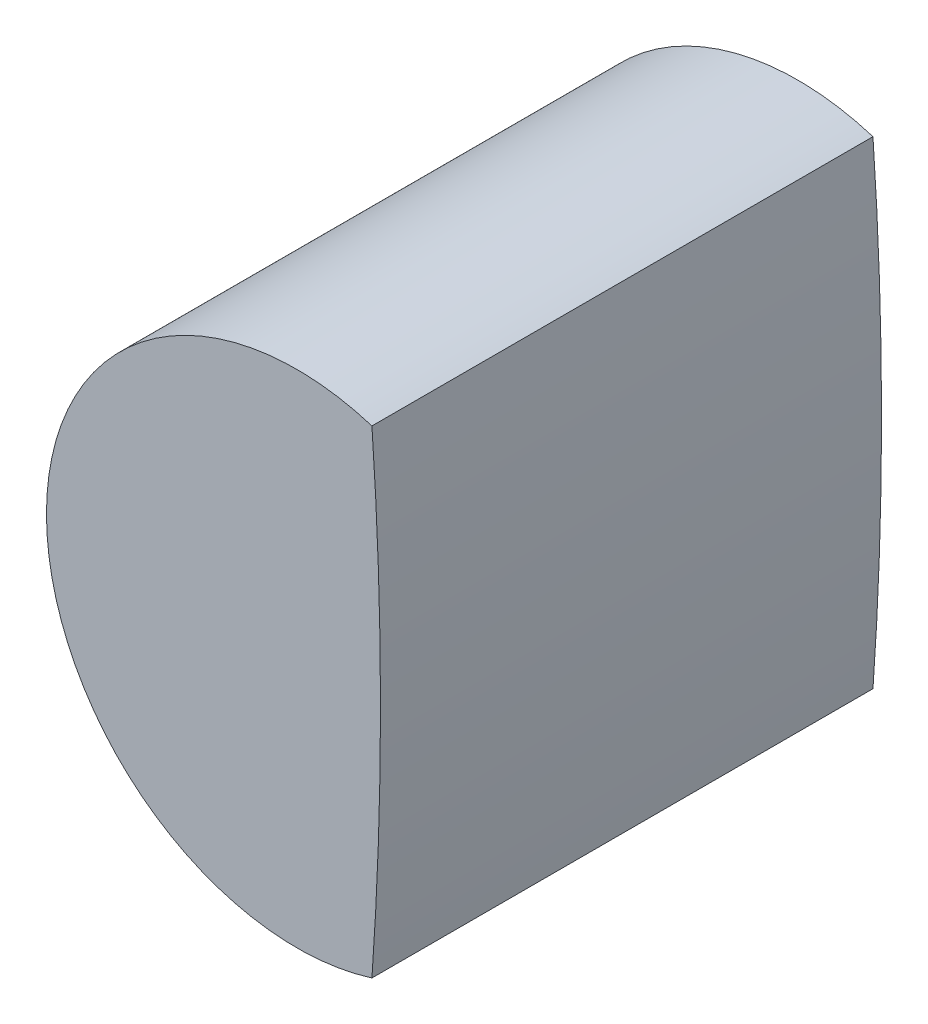
SolidWorks part; units mm, degrees
material "Acrylique (impact moyen-haut)"
ref_plane "Plan de face" through (0, 0, 0) normal (0, 0, 1) x (1, 0, 0)
ref_plane "Plan de dessus" through (0, 0, 0) normal (0, 1, 0) x (1, 0, 0)
ref_plane "Plan de droite" through (0, 0, 0) normal (1, 0, 0) x (0, 0, -1)
sketch "Esquisse1" plane through (0, 0, 0) normal (0, 0, 1) x (1, 0, 0)
  line L0 (0, 0) -> (-19.5, 0) construction
  arc A0 (0.4487, 1.4313) -> (0.4487, -1.4313) centre (0, 0) ccw
  arc A1 (0.4487, -1.4313) -> (0.4487, 1.4313) centre (-19.5, 0) ccw
  dimension "D1" = 3
  dimension "D3" = 40
  dimension "D2" = 19.5
extrude "Boss.-Extru.1" add sketch "Esquisse1" along normal blind 3
